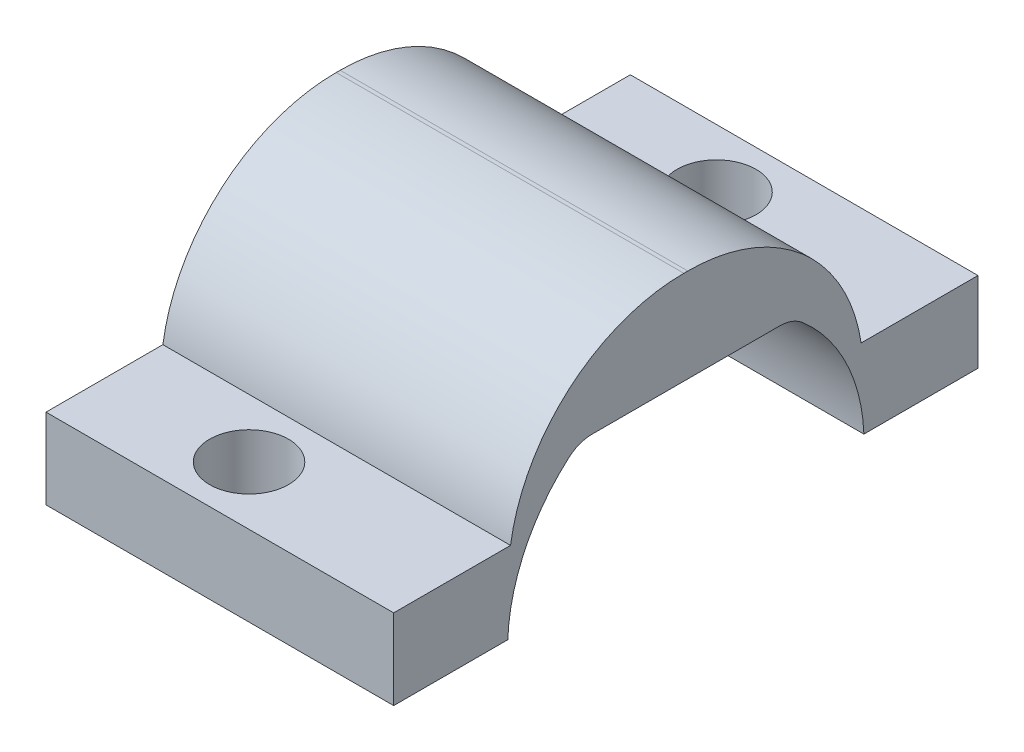
SolidWorks part; units mm, degrees
ref_plane "Plano frontal" through (0, 0, 0) normal (0, 0, 1) x (1, 0, 0)
ref_plane "Plano superior" through (0, 0, 0) normal (0, 1, 0) x (1, 0, 0)
ref_plane "Plano direito" through (0, 0, 0) normal (1, 0, 0) x (0, 0, -1)
sketch "Esboço1" plane through (0, 0, 0) normal (1, 0, 0) x (0, 0, -1)
  line L0 (0, -6.1) -> (0, -5.1)
  line L1 (0, 6.1) -> (0, 4.9)
  line L2 (-6.1, 0) -> (6.1, 0)
  line L3 (-3.6332, 4.9) -> (3.6332, 4.9)
  line L4 (-6.1, 0) -> (-10, 0)
  line L5 (6.1, 0) -> (10, 0)
  line L6 (-10, 0) -> (-10, 3)
  line L7 (10, 0) -> (10, 3)
  line L8 (-10, 3) -> (-6, 3)
  line L9 (-6, 3) -> (-6, 8.1)
  line L10 (-6, 8.1) -> (6, 8.1)
  line L11 (10, 3) -> (6, 3)
  line L12 (6, 3) -> (6, 8.1)
  circle A0 centre (0, 0) radius 6.1
  point P12 (0, 4.9)
  dimension "D1" = 12.2
  dimension "D2" = 1.2
  dimension "D3" = 1
  dimension "D4" = 3.9
  dimension "D5" = 3.9
  dimension "D6" = 3
  dimension "D7" = 3
  dimension "D8" = 2
extrude "Ressalto-extrusão1" add sketch "Esboço1" along normal blind 13.9 contours A0 L5 L7 L11 L12 L10 L9 L8 L6 L4 | L1 A0 L3 | L3 A0 L1 region at (0, 5.3843, -1.3823) region at (0, 5.9971, 1.9808) region at (0, 5.3843, 1.3823)
fillet "Filete1" radius 6 2 edges at (6.95, 8.1, 6) (6.95, 8.1, -6)
sketch "Esboço2" plane through (0, 3, 0) normal (0, 1, 0) x (1, 0, 0)
  line L0 (6.95, -6) -> (6.95, -10)
  line L1 (13.9, -6) -> (0, -6) construction
  line L2 (13.9, -10) -> (0, -10) construction
  line L3 (6.95, 6) -> (6.95, 10)
  line L4 (13.9, 6) -> (0, 6) construction
  line L5 (13.9, 10) -> (0, 10) construction
  circle A0 centre (6.95, 8) radius 1.35
  circle A1 centre (6.95, -8) radius 1.35
  dimension "D1" = 2.7
  dimension "D2" = 2.7
extrude "Corte-extrusão1" cut sketch "Esboço2" against normal blind 13.9 contours L3 A0 | L3 A0 | L0 A1 | L0 A1 region at (7.523, 3, 8) region at (6.377, 3, 8) region at (6.377, 3, -8) region at (7.523, 3, -8)
fillet "Filete2" radius 1.2 2 edges at (6.95, 4.9, -3.6332) (6.95, 4.9, 3.6332)
sketch "Esboço3" plane through (0, 3, 0) normal (0, 1, 0) x (1, 0, 0)
  line L0 (0, 10) -> (2, 10)
  line L1 (0, 10) -> (0, -10.0535)
  line L2 (2, 10) -> (2, -10.0535)
  line L3 (0, -10.0535) -> (2, -10.0535)
  line L4 (13.9, 10) -> (0, 10) construction
  dimension "D1" = 2
extrude "Corte-extrusão2" cut sketch "Esboço3" against normal through all both and the other way through all
sketch "Esboço4" plane through (2, 0, 0) normal (-1, 0, 0) x (0, 0, 1)
  line L0 (-10, 0) -> (-10, 0.25)
  line L1 (-10, 0) -> (10.133, 0)
  line L2 (-10, 0.25) -> (10.133, 0.25)
  line L3 (10.133, 0) -> (10.133, 0.25)
  line L4 (-10, 0) -> (-10, 3) construction
  dimension "D1" = 0.25
extrude "Corte-extrusão4" cut sketch "Esboço4" against normal through all
